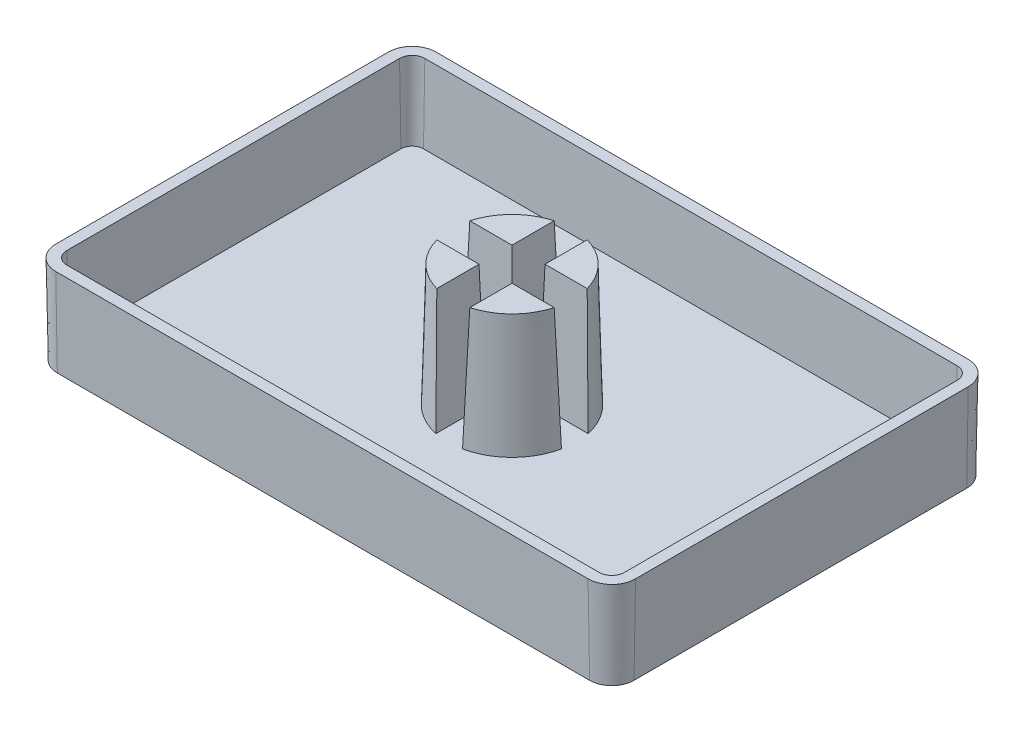
SolidWorks part; units mm, degrees
ref_plane "Front Plane" through (0, 0, 0) normal (0, 0, 1) x (1, 0, 0)
ref_plane "Top Plane" through (0, 0, 0) normal (0, 1, 0) x (1, 0, 0)
ref_plane "Right Plane" through (0, 0, 0) normal (1, 0, 0) x (0, 0, -1)
sketch "Sketch1" plane through (0, 0, 0) normal (0, 1, 0) x (1, 0, 0)
  line L1 (-12, -8.5) -> (12, -8.5)
  line L2 (-13, -7.5) -> (-13, 7.5)
  line L3 (-12, 8.5) -> (12, 8.5)
  line L4 (13, -7.5) -> (13, 7.5)
  line L5 (-13, -8.5) -> (13, 8.5) construction
  line L6 (-13, 8.5) -> (13, -8.5) construction
  arc A0 (-13, 7.5) -> (-12, 8.5) centre (-12, 7.5) cw
  arc A1 (13, 7.5) -> (12, 8.5) centre (12, 7.5) ccw
  arc A2 (13, -7.5) -> (12, -8.5) centre (12, -7.5) cw
  arc A3 (-12, -8.5) -> (-13, -7.5) centre (-12, -7.5) cw
  point P0 (0, 0)
  dimension "D3" = 1
  dimension "D1" = 26
  dimension "D2" = 17
extrude "Boss-Extrude1" add sketch "Sketch1" along normal blind 4 draft 1 draft outward yes
shell "Shell1" thickness 0.5 removed face at (0, 4, 0)
sketch "Sketch2" plane through (0, 0.5, 0) normal (0, 1, 0) x (1, 0, 0)
  line L0 (-0.6, -2.8298) -> (-0.6, -0.6)
  line L1 (2.8298, 0.6) -> (0.6, 0.6)
  line L2 (0, -2.2) -> (0, 2.2) construction
  line L3 (-2.2, 0) -> (2.2, 0) construction
  line L4 (2.8298, -0.6) -> (0.6, -0.6)
  line L5 (0.6, -2.8298) -> (0.6, -0.6)
  line L6 (-0.6, 0.6) -> (-0.6, 2.8298)
  line L7 (0.6, 0.6) -> (0.6, 2.8298)
  line L8 (-0.6, -0.6) -> (-2.8298, -0.6)
  line L9 (-0.6, 0.6) -> (-2.8298, 0.6)
  arc A0 (-2.8298, -0.6) -> (-0.6, -2.8298) centre (0, 0) ccw
  arc A1 (2.8298, 0.6) -> (0.6, 2.8298) centre (0, 0) ccw
  arc A2 (0.6, -2.8298) -> (2.8298, -0.6) centre (0, 0) ccw
  arc A3 (-0.6, 2.8298) -> (-2.8298, 0.6) centre (0, 0) ccw
  dimension "D1" = 0.6
  dimension "D2" = 0.6
extrude "Boss-Extrude2" add sketch "Sketch2" along normal blind 5.5 draft 1.5
